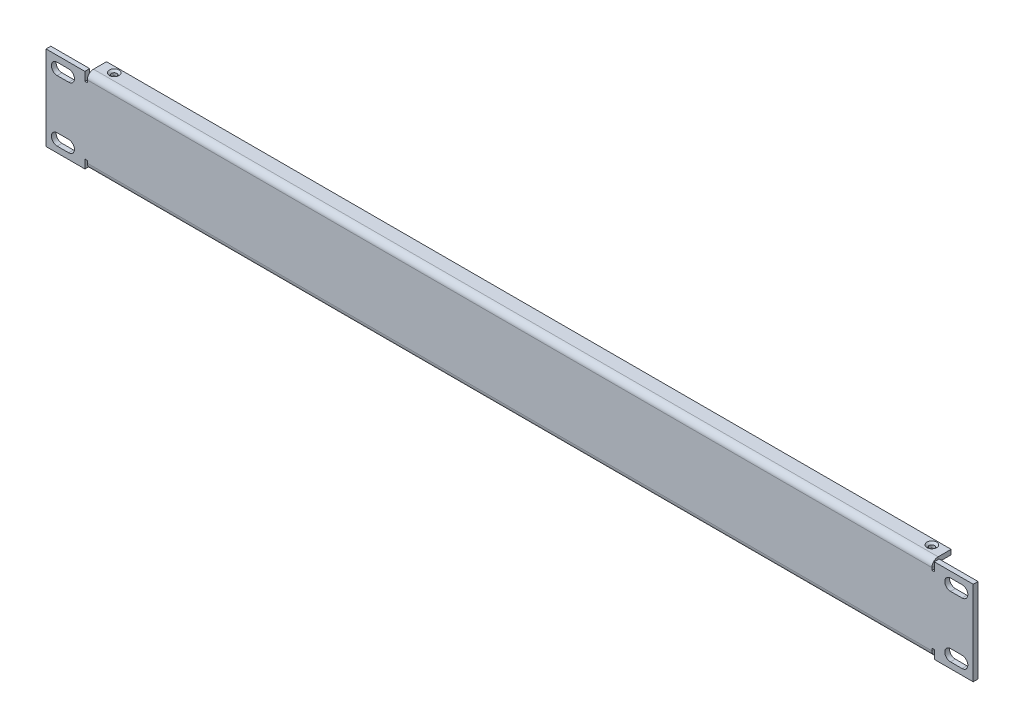
SolidWorks part; units mm, degrees
note: The reader was unsure of these and kept them because the rebuilt part matched: flange length of "Edge-Flange-Mouning".
ref_plane "Front Plane" through (0, 0, 0) normal (0, 0, 1) x (1, 0, 0)
ref_plane "Top Plane" through (0, 0, 0) normal (0, 1, 0) x (1, 0, 0)
ref_plane "Right Plane" through (0, 0, 0) normal (1, 0, 0) x (0, 0, -1)
sketch "Sketch1" plane through (0, 0, 0) normal (0, 0, 1) x (1, 0, 0)
  line L1 (0, 0) -> (-241.3, 0)
  line L2 (0, 0) -> (0, 22)
  line L3 (0, 22) -> (-241.3, 22)
  line L4 (-241.3, 0) -> (-241.3, 22)
  dimension "D1" = 22
  dimension "D2" = 241.3
sheet metal parameters "Sheet-Metal" thickness 2.5 parameters "D1"=0.7366
base flange "Base-Flange" sketch "Sketch1" thickness 2.5 reverse thickness direction no parameters "D1"=0.7366
edge flange "Edge-Flange-Mouning" sketch "Sketch12" flange angle 90 flange length 10 flange position material inside bend radius 0.7366 thickness 2.5 parameters "D6"=10
sketch "Sketch12" plane through (0, 22, -2.5) normal (0, 1, 0) x (1, 0, 0)
  line L0 (0, 0) -> (-241.3, 0) construction
  line L1 (0, 0) -> (-219.8, 0)
  line L2 (-219.8, 0) -> (-219.8, 7.5)
  line L3 (-219.8, 7.5) -> (0, 7.5)
  line L4 (0, 7.5) -> (0, 0)
  line L6 (-241.3, 0) -> (-241.3, -2.5) construction
  dimension "D1" = 21.5
bend "EdgeBend1" bend radius 0.7366 bend angle 90 parameters "D5"=1
sketch "Sketch13" plane through (0, 0, 0) normal (0, 0, 1) x (1, 0, 0)
  line L0 (-241.3, 0) -> (0, 0) construction
  line L2 (0, 0) -> (0, 18.7634) construction
  line L5 (-229.5, 15.9) -> (-235.5, 15.9) construction
  line L6 (-229.5, 12.9) -> (-235.5, 12.9)
  line L7 (-229.5, 18.9) -> (-235.5, 18.9)
  arc A2 (-229.5, 12.9) -> (-229.5, 18.9) centre (-229.5, 15.9) ccw
  arc A3 (-235.5, 18.9) -> (-235.5, 12.9) centre (-235.5, 15.9) ccw
  point P0 (-232.5, 15.9)
  point P13 (-232.5, 15.9)
  dimension "D3" = 232.5
  dimension "D1" = 15.9
extrude "Cut-Extrude-Mounting" cut sketch "Sketch13" against normal blind 2.5
hole_wizard "CSK for #3 Flat Head Machine Screw (100)1" positions "Sketch15" profile "Sketch14" countersink size "#3" standard "ANSI Inch" end condition up to next
sketch "Sketch15" plane through (0, 22, 0) normal (0, 1, 0) x (1, 0, 0)
  line L0 (-219.8, 10) -> (-219.8, 3.2366) construction
  line L1 (0, 10) -> (-219.8, 10) construction
  point P0 (-212.8, 7)
  dimension "D1" = 7
  dimension "D2" = 3
sketch "Sketch14" plane through (-212.8, 22, -7) normal (1, 0, 0) x (0, 0, 1)
  line L0 (0, 0) -> (0, 2.5)
  line L1 (0, 2.5) -> (1.397, 2.5)
  line L2 (1.397, 2.5) -> (1.397, 0.9484)
  line L3 (1.397, 0.9484) -> (2.5273, 0)
  line L5 (2.5273, 0) -> (0, 0)
  line L6 (-1.397, 0.9484) -> (-2.5273, 0) construction
  line L11 (0, -6.35) -> (0, 107.95) construction
  dimension "Thru Hole Dia." = 2.794
  dimension "Thru Hole Depth" = 2.5
  dimension "Near C'Sink Dia." = 5.0546
  dimension "Near C'Sink Angle" = 100
mirror "Mirror-Vertical" about plane through (0, 0, -2.5) normal (1, 0, 0) of bodies 104
mirror "Mirror-Horizontal"
bend "MirrorBend1" bend radius 0.7366 bend angle 90 parameters "D5"=2
flat pattern "Flat-Pattern1" [suppressed]
sketch "Bend-Lines1" plane through (0, 0, 0) normal (0, 0, 1) x (1, 0, 0)
  line L0 (-219.8, -20.3237) -> (219.8, -20.3237) construction
  line L1 (219.8, 20.3237) -> (-219.8, 20.3237) construction
  line L2 (-219.8, -20.3237) -> (219.8, -20.3237) construction
  line L3 (219.8, 20.3237) -> (-219.8, 20.3237) construction
sketch3d "Bounding-Box1" [suppressed]
  line L0 (-241.3, -28.6473, 0) -> (241.3, -28.6473, 0) construction
  line L1 (-241.3, 28.6473, 0) -> (241.3, 28.6473, 0) construction
  line L2 (-241.3, -28.6473, 0) -> (-241.3, 28.6473, 0) construction
  line L3 (241.3, -28.6473, 0) -> (241.3, 28.6473, 0) construction
bend of the flat pattern "Flatten-<EdgeBend1>1"
bend of the flat pattern "Flatten-<MirrorBend1>1"
equation "\"RackUnitHeight\"= 44"
equation "\"RackUnitWidth\"= 482.6"
equation "\"RackUnitInnerWidth\"= 440"
equation "\"RackUnitMountingHoleHorizontalSpacing\"= 465"
equation "\"RackUnitMountingHoleVerticalSpacing\"= 15.9"
equation "\"D1@Sketch1\"  = \"RackUnitHeight@Rack Unit.sldasm\" / 2"
equation "\"D2@Sketch1\"  = \"RackUnitWidth@Rack Unit.sldasm\" / 2"
equation "\"D1@Sketch13\"  = \"RackUnitMountingHoleVerticalSpacing@Rack Unit.sldasm\""
equation "\"D2@Sketch13\" = \"RackUnitMountingHoleHorizontalSpacing\" / 2"
equation "\"D3@Sketch13\" = \"RackUnitMountingHoleHorizontalSpacing@Rack Unit.sldasm\" / 2"
